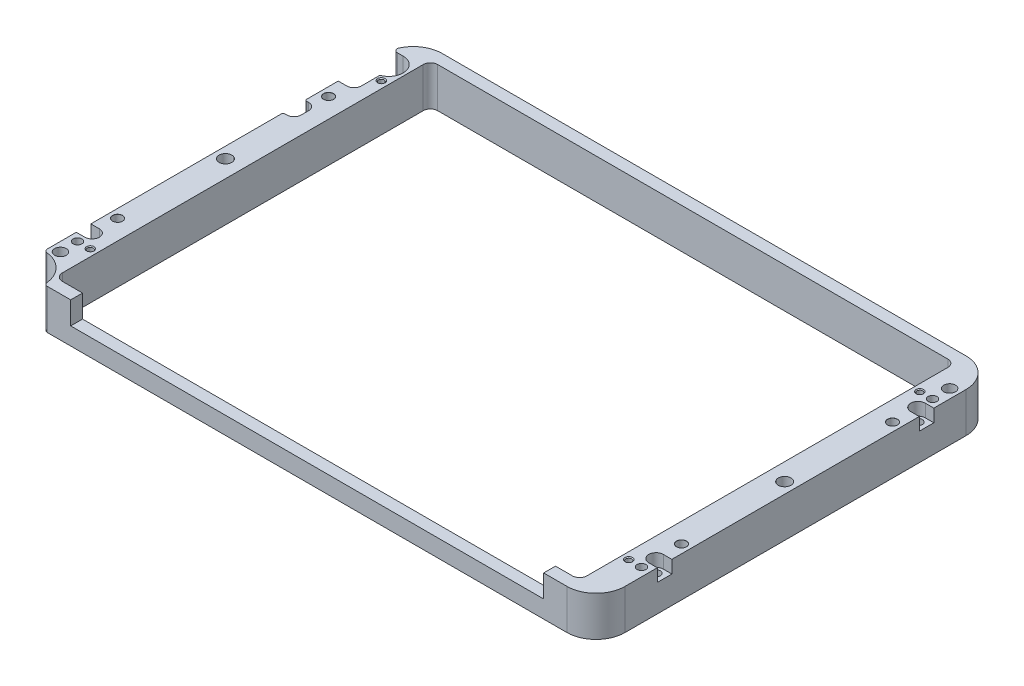
SolidWorks part; units mm, degrees
ref_plane "Front Plane" through (0, 0, 0) normal (0, 0, 1) x (1, 0, 0)
ref_plane "Top Plane" through (0, 0, 0) normal (0, 1, 0) x (1, 0, 0)
ref_plane "Right Plane" through (0, 0, 0) normal (1, 0, 0) x (0, 0, -1)
sketch "Sketch1" plane through (0, 0, 0) normal (0, 1, 0) x (1, 0, 0)
  line L1 (-79.85, 54.85) -> (79.85, 54.85)
  line L2 (-79.85, 54.85) -> (-79.85, -54.85)
  line L3 (-79.85, -54.85) -> (79.85, -54.85)
  line L4 (79.85, 54.85) -> (79.85, -54.85)
  line L5 (-79.85, 54.85) -> (79.85, -54.85) construction
  line L6 (-79.85, -54.85) -> (79.85, 54.85) construction
  line L7 (-72.1, 51.6) -> (72.1, 51.6)
  line L8 (-72.1, 51.6) -> (-72.1, -51.6)
  line L9 (-72.1, -51.6) -> (72.1, -51.6)
  line L10 (72.1, 51.6) -> (72.1, -51.6)
  line L11 (-72.1, 51.6) -> (72.1, -51.6) construction
  line L12 (-72.1, -51.6) -> (72.1, 51.6) construction
  point P0 (0, 0)
  point P6 (0, 0)
  dimension "D1" = 159.7
  dimension "D2" = 109.7
  dimension "D3" = 103.2
  dimension "D4" = 144.2
extrude "Boss-Extrude1" add sketch "Sketch1" along normal blind 11
sketch "Sketch4_riser_bolts" plane through (0, 11, 0) normal (0, 1, 0) x (1, 0, 0)
  line L1 (-77.5, 36) -> (77.5, 36) construction
  line L2 (-77.5, 36) -> (-77.5, -36) construction
  line L3 (-77.5, -36) -> (77.5, -36) construction
  line L4 (77.5, 36) -> (77.5, -36) construction
  line L5 (-77.5, 36) -> (77.5, -36) construction
  line L6 (-77.5, -36) -> (77.5, 36) construction
  point P0 (0, 0)
  dimension "D1" = 72
  dimension "D2" = 155
hole_wizard "Ø2.4 (2.4) Diameter Hole1" positions "Sketch24" profile "Sketch26" hole size "Ø2.4" standard "ANSI Metric" end condition through all
sketch "Sketch24" plane through (0, 11, 0) normal (0, 1, 0) x (1, 0, 0)
  point P0 (-77.5, 36)
  point P3 (77.5, 36)
  point P6 (-77.5, -36)
  point P9 (77.5, -36)
sketch "Sketch26" plane through (-77.5, 11, -36) normal (1, 0, 0) x (0, 0, 1)
  line L0 (0, 0) -> (0, 11)
  line L1 (0, 11) -> (1.2, 11)
  line L2 (1.2, 11) -> (1.2, 0)
  line L5 (1.2, 0) -> (0, 0)
  line L11 (0, -6.35) -> (0, 107.95) construction
  dimension "Thru Hole Dia." = 2.4
  dimension "Thru Hole Depth" = 11
sketch "Sketch29" plane through (0, 11, 0) normal (0, 1, 0) x (1, 0, 0)
  line L0 (-77.5, 36) -> (-77.5, -36) construction
  line L1 (-77.5, 38) -> (-79.85, 38)
  line L2 (-79.85, 38) -> (-79.85, 34)
  line L3 (-79.85, 54.85) -> (-79.85, -54.85) construction
  line L4 (-79.85, 34) -> (-77.5, 34)
  arc A0 (-77.5, 38) -> (-77.5, 34) centre (-77.5, 36) cw
  dimension "D2" = 2
  dimension "D1" = 4
extrude "Cut-Extrude10" cut sketch "Sketch29" against normal blind 3.5
pattern_linear "LPattern1" count 2 spacing 72 along (0, 0, 1) of "Cut-Extrude10"
mirror "Mirror2" about plane through (0, 0, 0) normal (1, 0, 0) of "LPattern1"
sketch "Sketch10" plane through (0, 11, 0) normal (0, 1, 0) x (1, 0, 0)
  line L1 (74, -40) -> (-74, -40) construction
  line L2 (74, -40) -> (74, 40) construction
  line L3 (74, 40) -> (-74, 40) construction
  line L4 (-74, -40) -> (-74, 40) construction
  line L5 (74, -40) -> (-74, 40) construction
  line L6 (74, 40) -> (-74, -40) construction
  point P0 (0, 0)
  dimension "D1" = 148
  dimension "D2" = 80
hole_wizard "M2x0.4 Tapped Hole1" positions "Sketch5" profile "Sketch6" tap size "M2x0.4" standard "ANSI Metric"
sketch "Sketch5" plane through (0, 11, 0) normal (0, 1, 0) x (1, 0, 0)
  point P13 (-74, 40)
  point P16 (-74, -40)
  point P19 (74, 40)
  point P22 (74, -40)
sketch "Sketch6" plane through (-74, 11, -40) normal (1, 0, 0) x (0, 0, 1)
  line L0 (0, 0) -> (0, 3.9807)
  line L1 (0, 3.9807) -> (0.8, 3.5)
  line L2 (0.8, 3.5) -> (0.8, 0.225)
  line L3 (0.8, 0.225) -> (1.025, 0)
  line L5 (1.025, 0) -> (0, 0)
  line L6 (-0.8, 0.225) -> (-1.025, 0) construction
  line L10 (0, 3.9807) -> (-0.8, 3.5) construction
  line L11 (0, -6.35) -> (0, 107.95) construction
  dimension "Tap Drill Dia." = 1.6
  dimension "Tap Drill Depth" = 3.5
  dimension "Near C'Sink Dia." = 2.05
  dimension "Near C'Sink Angle" = 90
  dimension "Drill Angle" = 118
cosmetic thread "Hole Thread5" parameters "D1"=4, "D2"=2
cosmetic thread "Hole Thread6" parameters "D1"=4, "D2"=2
cosmetic thread "Hole Thread7" parameters "D1"=4, "D2"=2
cosmetic thread "Hole Thread8" parameters "D1"=4, "D2"=2
sketch "Sketch7" plane through (0, 11, 0) normal (0, 1, 0) x (1, 0, 0)
  line L0 (79.85, 54.85) -> (-79.85, 54.85) construction
  line L2 (-76.85, 48.85) -> (-79.85, 48.85)
  line L3 (-79.85, 54.85) -> (-79.85, 38) construction
  line L5 (-79.85, 48.85) -> (-79.85, 40.85)
  line L6 (-79.85, 40.85) -> (-76.85, 40.85)
  line L7 (-79.85, 54.85) -> (-79.85, 38) construction
  circle A0 centre (-76.85, 44.85) radius 4 construction
  arc A2 (-76.85, 48.85) -> (-76.85, 40.85) centre (-76.85, 44.85) cw
  dimension "D1" = 8
  dimension "D2" = 10
  dimension "D3" = 3
sketch "Sketch9" plane through (0, 11, 0) normal (0, 1, 0) x (1, 0, 0)
  line L0 (-76.85, 4) -> (-76.85, -4) construction
  line L1 (-74.85, 4) -> (-74.85, -4)
  line L2 (-78.85, 4) -> (-78.85, -4)
  line L3 (0, 0) -> (-76.85, 0) construction
  line L5 (-79.85, -38) -> (-79.85, -54.85) construction
  arc A0 (-74.85, 4) -> (-78.85, 4) centre (-76.85, 4) ccw
  arc A1 (-78.85, -4) -> (-74.85, -4) centre (-76.85, -4) ccw
  point P2 (-76.85, 0)
  point P10 (-76.85, 6)
  point P11 (-76.85, -6)
  dimension "D1" = 4
  dimension "D2" = 12
  dimension "D3" = 1
extrude "Cut-Extrude3" [suppressed] cut sketch "Sketch9" against normal blind 0.5
mirror "Mirror1" [suppressed] about plane through (0, 0, 0) normal (1, 0, 0)
sketch "Sketch11" plane through (0, 11, 0) normal (0, 1, 0) x (1, 0, 0)
  line L0 (-79.85, 42) -> (-79.85, 36)
  line L1 (77.5, -40) -> (-77.5, -40) construction
  line L2 (77.5, -40) -> (77.5, 40) construction
  line L3 (77.5, 40) -> (-77.5, 40) construction
  line L4 (-77.5, -40) -> (-77.5, 40) construction
  line L5 (77.5, -40) -> (-77.5, 40) construction
  line L6 (77.5, 40) -> (-77.5, -40) construction
  line L8 (-79.85, 36) -> (-75.5, 36)
  line L9 (-79.85, 42) -> (-75.5, 42)
  line L10 (-75.5, 42) -> (-75.5, 36)
  line L11 (-79.85, 54.85) -> (-79.85, 38) construction
  arc A0 (-77.5, 34) -> (-77.5, 38) centre (-77.5, 36) ccw construction
  point P0 (0, 0)
  dimension "D1" = 155
  dimension "D2" = 80
  dimension "D3" = 6
extrude "Cut-Extrude4" cut sketch "Sketch11" against normal up to surface (3.5 mm away) up to face at (-78.175, 7.5, -36)
sketch "Sketch30" plane through (0, 7.5, 0) normal (0, 1, 0) x (1, 0, 0)
  line L0 (-75.5, 40) -> (-75.5, 42)
  line L1 (-75.5, 42) -> (-79.85, 42)
  line L2 (-79.85, 42) -> (-79.85, 38)
  line L3 (-79.85, 42) -> (-79.85, 34) construction
  line L4 (-79.85, 38) -> (-77.5, 38)
  line L5 (-75.5, 36) -> (-75.5, 42) construction
  circle A0 centre (-77.5, 40) radius 2 construction
  arc A1 (-77.5, 38) -> (-75.5, 40) centre (-77.5, 40) ccw
  dimension "D1" = 4
  dimension "D2" = 4
extrude "Cut-Extrude11" cut sketch "Sketch30" against normal through all and the other way through all
hole_wizard "Ø2.4 (2.4) Diameter Hole2" positions "Sketch27" profile "Sketch28" hole size "Ø2.4" standard "ANSI Metric" end condition through all
sketch "Sketch27" plane through (0, 11, 0) normal (0, 1, 0) x (1, 0, 0)
  point P0 (-77.5, -40)
  point P3 (77.5, 40)
  point P6 (77.5, -40)
sketch "Sketch28" plane through (-77.5, 11, 40) normal (1, 0, 0) x (0, 0, 1)
  line L0 (0, 0) -> (0, 11)
  line L1 (0, 11) -> (1.2, 11)
  line L2 (1.2, 11) -> (1.2, 0)
  line L5 (1.2, 0) -> (0, 0)
  line L11 (0, -6.35) -> (0, 107.95) construction
  dimension "Thru Hole Dia." = 2.4
  dimension "Thru Hole Depth" = 11
sketch "Sketch15" plane through (0, 11, 0) normal (0, 1, 0) x (1, 0, 0)
  line L1 (77.5, -29) -> (-77.5, -29) construction
  line L2 (77.5, -29) -> (77.5, 29) construction
  line L3 (77.5, 29) -> (-77.5, 29) construction
  line L4 (-77.5, -29) -> (-77.5, 29) construction
  line L5 (77.5, -29) -> (-77.5, 29) construction
  line L6 (77.5, 29) -> (-77.5, -29) construction
  point P0 (0, 0)
  dimension "D1" = 155
  dimension "D2" = 58
hole_wizard "Ø2.7 (2.7) Diameter Hole1" positions "Sketch16" profile "Sketch17" hole size "Ø2.7" standard "ANSI Metric" end condition through all
sketch "Sketch16" plane through (0, 11, 0) normal (0, 1, 0) x (1, 0, 0)
  point P0 (-77.5, 29)
  point P3 (-77.5, -29)
  point P6 (77.5, 29)
  point P9 (77.5, -29)
sketch "Sketch17" plane through (-77.5, 11, -29) normal (1, 0, 0) x (0, 0, 1)
  line L0 (0, 0) -> (0, 11)
  line L1 (0, 11) -> (1.35, 11)
  line L2 (1.35, 11) -> (1.35, 0.025)
  line L3 (1.35, 0.025) -> (1.375, 0)
  line L5 (1.375, 0) -> (0, 0)
  line L6 (-1.35, 0.025) -> (-1.375, 0) construction
  line L11 (0, -6.35) -> (0, 107.95) construction
  dimension "Thru Hole Dia." = 2.7
  dimension "Thru Hole Depth" = 11
  dimension "Near C'Sink Dia." = 2.75
  dimension "Near C'Sink Angle" = 90
sketch "Sketch18" plane through (0, 11, 0) normal (0, 1, 0) x (1, 0, 0)
  line L0 (-79.85, 21.85) -> (-77.85, 21.85) construction
  line L1 (79.85, 54.85) -> (-79.85, 54.85) construction
  line L2 (-79.85, -38) -> (-79.85, -54.85) construction
  line L3 (-78.85, 24.85) -> (-79.85, 24.85)
  line L4 (-79.85, 34) -> (-79.85, -34) construction
  line L5 (-79.85, 24.85) -> (-79.85, 18.85)
  line L6 (-79.85, 18.85) -> (-78.85, 18.85)
  line L7 (-76.85, 22.85) -> (-76.85, 20.85)
  circle A0 centre (-77.85, 21.85) radius 0.65 construction
  arc A1 (-78.85, 24.85) -> (-76.85, 22.85) centre (-78.85, 22.85) cw
  arc A2 (-76.85, 20.85) -> (-78.85, 18.85) centre (-78.85, 20.85) cw
  dimension "D1" = 1.3
  dimension "D5" = 2
  dimension "D6" = 2
  dimension "D2" = 2
  dimension "D3" = 33
  dimension "D4" = 6
  dimension "D7" = 3
extrude "Cut-Extrude6" cut sketch "Sketch18" against normal through all
sketch "Sketch19" plane through (0, 11, 0) normal (0, 1, 0) x (1, 0, 0)
  line L4 (-77.35, -44.85) -> (77.35, -44.85) construction
  line L5 (-77.35, -44.85) -> (-77.35, 44.85) construction
  line L6 (-77.35, 44.85) -> (77.35, 44.85) construction
  line L7 (77.35, -44.85) -> (77.35, 44.85) construction
  line L8 (-77.35, -44.85) -> (77.35, 44.85) construction
  line L9 (-77.35, 44.85) -> (77.35, -44.85) construction
  circle A0 centre (77.35, 44.85) radius 1.6
  circle A1 centre (-77.35, -44.85) radius 1.6
  point P2 (0, 0)
  dimension "D1" = 3.2
  dimension "D2" = 154.7
  dimension "D3" = 89.7
extrude "Cut-Extrude7" cut sketch "Sketch19" against normal blind 3.5
sketch "Sketch32" plane through (0, 0, 0) normal (0, -1, 0) x (1, 0, 0)
  line L1 (77.35, -44.85) -> (-77.35, -44.85) construction
  line L2 (77.35, -44.85) -> (77.35, 44.85) construction
  line L3 (77.35, 44.85) -> (-77.35, 44.85) construction
  line L4 (-77.35, -44.85) -> (-77.35, 44.85) construction
  line L5 (77.35, -44.85) -> (-77.35, 44.85) construction
  line L6 (77.35, 44.85) -> (-77.35, -44.85) construction
  circle A0 centre (-77.35, 44.85) radius 1.375
  circle A1 centre (77.35, -44.85) radius 1.375
  point P0 (0, 0)
  dimension "D1" = 2.75
extrude "Boss-Extrude2" [suppressed] add sketch "Sketch32" along normal blind 1
extrude "Cut-Extrude8" cut sketch "Sketch7" against normal through all
sketch "Sketch8" plane through (0, 11, 0) normal (0, 1, 0) x (1, 0, 0)
  line L0 (-79.85, -54.85) -> (79.85, -54.85) construction
  line L2 (-79.85, -38) -> (-79.85, -54.85) construction
  line L3 (-76.15, -51.15) -> (-79.85, -54.85) construction
  circle A0 centre (-76.15, -51.15) radius 1.9 construction
  circle A1 centre (-79.85, -54.85) radius 8
  dimension "D1" = 3.8
  dimension "D4" = 16
  dimension "D2" = 3.7
  dimension "D3" = 3.7
extrude "Cut-Extrude9" cut sketch "Sketch8" against normal through all
fillet "Fillet1" radius 2 4 edges at (-72.1, 5.5, 51.6) (72.1, 5.5, 51.6) (72.1, 5.5, -51.6) (-72.1, 5.5, -51.6)
fillet "Fillet2" radius 8 3 edges at (79.85, 5.5, 54.85) (79.85, 5.5, -54.85) (-79.85, 5.5, -54.85)
fillet "Fillet3" radius 1 3 edges at (-79.85, 5.5, -48.85) (-71.85, 5.5, 54.85) (-79.85, 5.5, 46.85)
fillet "Fillet4" radius 2 1 edges at (-79.85, 3.75, -38)
fillet "Fillet5" radius 0.5 2 edges at (-79.85, 5.5, -18.85) (-79.85, 5.5, -24.85)
sketch "Sketch31" plane through (0, 11, 0) normal (0, 1, 0) x (1, 0, 0)
  line L0 (70.1, 51.6) -> (-70.1, 51.6) construction
  line L1 (-24, 51.6) -> (24, 51.6)
  line L2 (-24, 51.6) -> (-24, 52.95)
  line L3 (-24, 52.95) -> (24, 52.95)
  line L4 (24, 51.6) -> (24, 52.95)
  line L5 (0, 0) -> (0, 51.6) construction
  line L6 (71.85, 54.85) -> (-72.104, 54.85) construction
  dimension "D1" = 1.9
  dimension "D2" = 48
extrude "Cut-Extrude12" [suppressed] cut sketch "Sketch31" against normal through all
mirror "Mirror3" [suppressed] about plane through (0, 0, 0) normal (0, 0, 1)
chamfer "Chamfer1" [suppressed] distance 1.6 angle 45
fillet "Fillet6" [suppressed] radius 2
ref_plane "Plane1" through (0, 5.5, 0) normal (0, 1, 0) x (1, 0, 0)
sketch "Sketch33" plane through (0, 0, 54.85) normal (0, 0, 1) x (1, 0, 0)
  line L0 (-70.9057, 11) -> (71.85, 11) construction
  line L7 (-64.5279, 11) -> (65.4721, 11)
  line L12 (-64.5279, 11) -> (-64.5279, 4.8)
  line L13 (-64.5279, 4.8) -> (65.4721, 4.8)
  line L14 (65.4721, 11) -> (65.4721, 4.8)
  point P6 (0.4721, 11)
  point P7 (0.4721, 11)
  dimension "D1" = 6.2
  dimension "D2" = 130
extrude "Cut-Extrude13" cut sketch "Sketch33" against normal up to next
sketch "Sketch34" plane through (0, 0, 0) normal (0, -1, 0) x (-1, 0, 0)
  line L13 (-75.4, -31.1) -> (-79.6, -31.1)
  line L14 (-75.4, -31.1) -> (-75.4, -26.9)
  line L15 (-75.4, -26.9) -> (-79.6, -26.9)
  line L16 (-79.6, -31.1) -> (-79.6, -26.9)
  line L17 (-75.4, -31.1) -> (-79.6, -26.9) construction
  line L18 (-75.4, -26.9) -> (-79.6, -31.1) construction
  point P12 (-77.5, -29)
  dimension "D1" = 4.2
extrude "Cut-Extrude14" cut sketch "Sketch34" against normal blind 2.5
mirror "Mirror4" about plane through (0, 0, 0) normal (0, 0, 1) of "Cut-Extrude14"
mirror "Mirror5" about plane through (0, 0, 0) normal (1, 0, 0) of "Mirror4"
sketch "Sketch35" plane through (0, 11, 0) normal (0, 1, 0) x (1, 0, 0)
  line L0 (-76.85, 4) -> (-76.85, -4) construction
  circle A2 centre (-76.85, 0) radius 1.75
  dimension "D1" = 3.5
extrude "Cut-Extrude15" cut sketch "Sketch35" against normal blind 4.5
sketch "Sketch38" plane through (0, 6.5, 0) normal (0, 1, 0) x (1, 0, 0)
  circle A0 centre (-76.85, 0) radius 1.25
  dimension "D1" = 2.5
extrude "Cut-Extrude17" cut sketch "Sketch38" against normal through all
mirror "Mirror7" about plane through (0, 0, 0) normal (1, 0, 0) of "Cut-Extrude17", "Cut-Extrude15"
